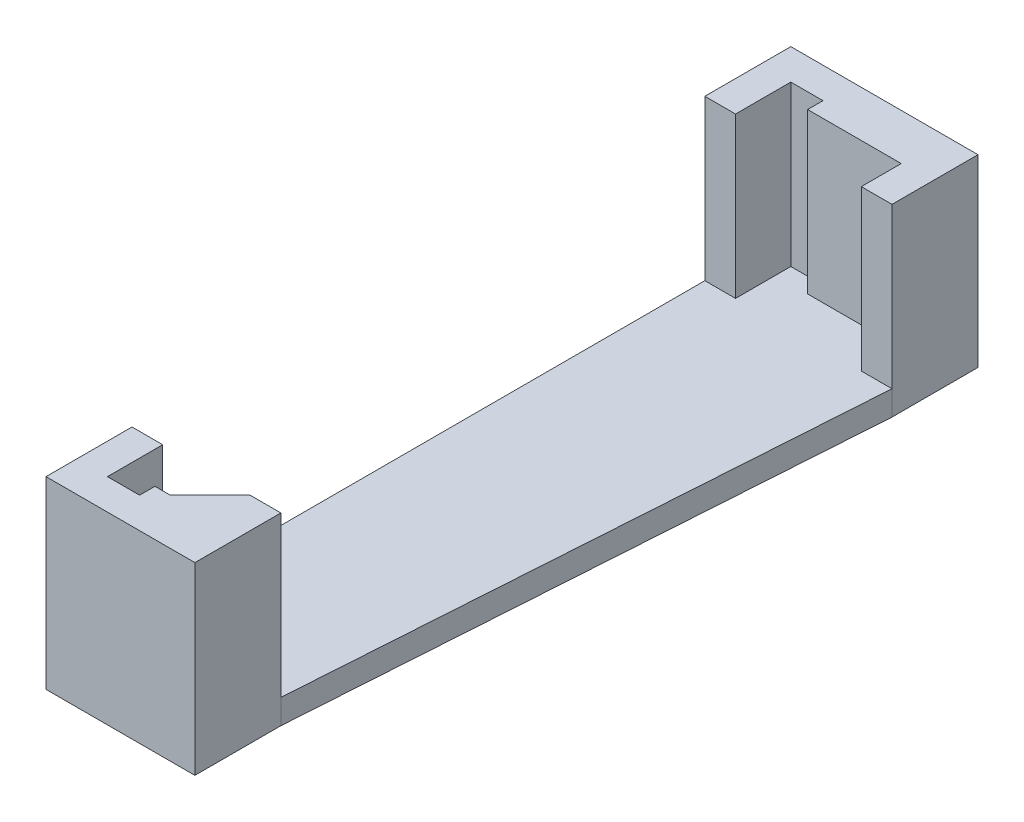
SolidWorks part; units mm, degrees
ref_plane "Front Plane" through (0, 0, 0) normal (0, 0, 1) x (1, 0, 0)
ref_plane "Top Plane" through (0, 0, 0) normal (0, 1, 0) x (1, 0, 0)
ref_plane "Right Plane" through (0, 0, 0) normal (1, 0, 0) x (0, 0, -1)
sketch "Sketch1" plane through (0, 0, 0) normal (0, 1, 0) x (1, 0, 0)
  line L1 (0, 0) -> (38.6999, 0)
  line L2 (0, 0) -> (0, 153.9875)
  line L3 (0, 153.9875) -> (38.6999, 153.9875)
  line L4 (38.6999, 0) -> (38.6999, 153.9875)
  dimension "D1" = 38.6999
  dimension "D2" = 153.9875
extrude "Boss-Extrude1" add sketch "Sketch1" along normal blind 5.08
sketch "Sketch3" plane through (0, 5.08, 0) normal (0, 1, 0) x (1, 0, 0)
  line L0 (6.65, 147.6375) -> (6.35, 147.6375)
  line L1 (6.65, 147.6375) -> (13, 147.6375)
  line L2 (13, 147.6375) -> (13, 144.4625)
  line L3 (13, 144.4625) -> (32.05, 144.4625)
  line L4 (6.35, 147.6375) -> (6.35, 136.2075)
  line L7 (32.05, 144.4625) -> (32.35, 144.4625)
  line L8 (32.35, 144.4625) -> (32.35, 136.2075)
  line L9 (32.35, 136.2075) -> (38.7, 136.2075)
  line L10 (38.7, 136.2075) -> (38.7, 153.9875)
  line L11 (38.7, 153.9875) -> (0, 153.9875)
  line L12 (6.35, 136.2075) -> (0, 136.2075)
  line L13 (0, 153.9875) -> (0, 136.2075)
  line L14 (38.6999, 153.9875) -> (0, 153.9875) construction
  line L15 (0, 153.9875) -> (0, 0) construction
  line L16 (13, 9.525) -> (16.175, 9.525)
  line L17 (9.825, 147.6375) -> (9.825, 76.9938) construction
  line L18 (9.825, 76.9938) -> (60.625, 76.9938) construction
  line L19 (30.78, 0) -> (0, 0)
  line L20 (30.78, 17.78) -> (30.78, 0)
  line L25 (13, 6.35) -> (13, 9.525)
  line L26 (6.65, 6.35) -> (13, 6.35)
  line L27 (6.65, 6.35) -> (6.35, 6.35)
  line L28 (6.35, 6.35) -> (6.35, 17.78)
  line L29 (6.35, 17.78) -> (0, 17.78)
  line L30 (0, 0) -> (0, 17.78)
  line L31 (16.175, 9.525) -> (24.43, 17.78)
  line L32 (24.43, 17.78) -> (30.78, 17.78)
  point P19 (9.825, 147.6375)
  point P23 (0, 0)
  point P32 (0, 0)
  line M5 (38.6999, 153.9875) -> (0, 153.9875)
  dimension "D1" = 19.05
  dimension "D2" = 6.35
  dimension "D3" = 3.175
  dimension "D4" = 11.43
  dimension "D5" = 0.3
  dimension "D6" = 0.3
  dimension "D7" = 0
  dimension "D8" = 0
  dimension "D9" = 6.35
  dimension "D10" = 6.35
  dimension "D11" = 6.35
  dimension "D12" = 0
  dimension "D13" = 70.6437
  dimension "D14" = 50.8
  dimension "D15" = 3.175
  dimension "D16" = 135
  dimension "D17" = 6.35
  dimension "D18" = 90
  dimension "D19" = 18.08
  dimension "D20" = 90
extrude "Boss-Extrude2" add sketch "Sketch3" along normal blind 33.02 contours L13 L12 L4 L0 L1 L2 L3 L7 L8 L9 L10 M5 | L30 L19 L20 L25 L26 L27 L28 L29 region at (19.8016, 5.08, -147.3128) region at (16.2049, 5.08, -7.4902)
sketch "Sketch4" plane through (0, 5.08, 0) normal (0, 1, 0) x (1, 0, 0)
  line L0 (30.78, 0) -> (38.6999, 0)
  line L1 (38.6999, 0) -> (38.6999, 136.2075)
  line L3 (38.6999, 136.2075) -> (30.78, 17.78)
  line L4 (30.78, 17.78) -> (30.78, 0)
extrude "Cut-Extrude1" cut sketch "Sketch4" against normal through all
